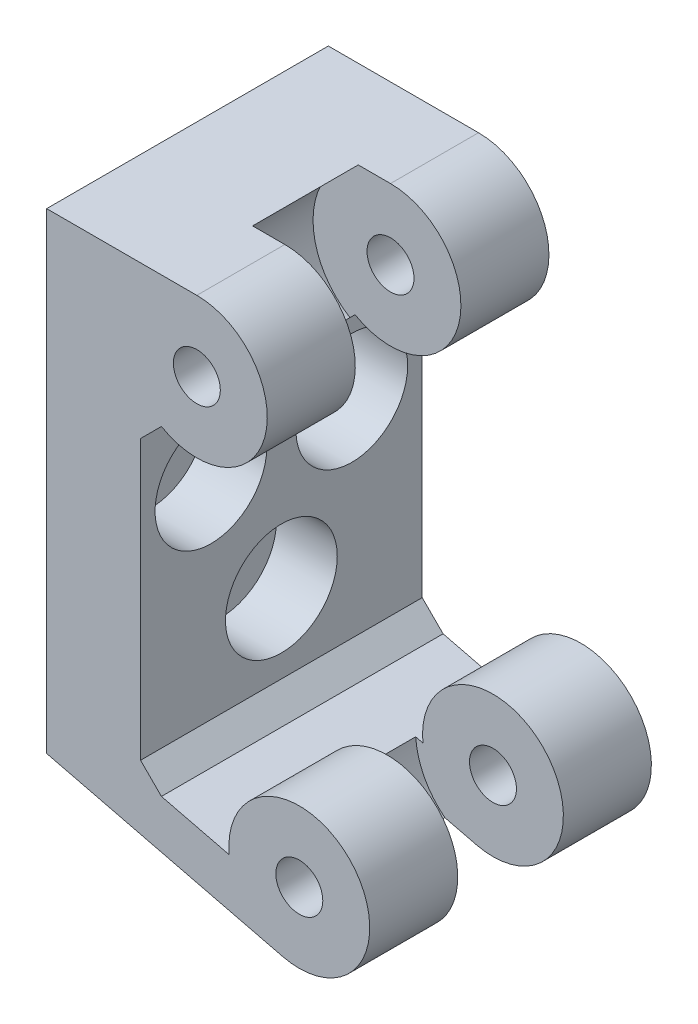
SolidWorks part; units mm, degrees
other "Markup1"
sketch "Sketch3" plane through (0, 0, 12) normal (0, 0, 1) x (1, 0, 0)
other "DetailItem1"
other "DetailItem3"
other "DetailItem5"
ref_plane "Front Plane" through (0, 0, 0) normal (0, 0, 1) x (1, 0, 0)
ref_plane "Top Plane" through (0, 0, 0) normal (0, 1, 0) x (1, 0, 0)
ref_plane "Right Plane" through (0, 0, 0) normal (1, 0, 0) x (0, 0, -1)
sketch "Sketch-optimization parameters" plane through (0, 0, 0) normal (0, 0, 1) x (1, 0, 0)
  line L2 (0, 0) -> (0, 20.1035)
  line L3 (0, 20.1035) -> (6.3989, 20.1035)
  line L5 (4.8896, 14.5108) -> (4, 13.6212)
  line L6 (4, 13.6212) -> (4, 1.7504)
  line L7 (4.8896, 0.8608) -> (7.7788, 0.1528)
  line L11 (6.3989, 17.1035) -> (10.764, 0.4507) construction
  line L16 (3.444, 0.5146) -> (10.764, 0.4507) construction
  line L17 (6.3989, -983.3033) -> (6.3989, 49016.6967) construction
  line L22 (4, 1.7504) -> (4.8896, 0.8608)
  line L23 (0, 0) -> (10.0499, -2.463)
  line L28 (-1000, 0) -> (49000, 0) construction
  line L29 (0, -1000) -> (0, 49000) construction
  line L30 (6.3655, 16.9158) -> (-8761.9708, -49208.2432) construction
  line L31 (-993.9512, 17.1035) -> (49006.0488, 17.1035) construction
  arc A0 (10.0499, -2.463) -> (7.7788, 0.1528) centre (10.764, 0.4507) ccw
  arc A1 (6.3989, 20.1035) -> (4.8896, 14.5108) centre (6.3989, 17.1035) cw
  circle A2 centre (6.3989, 17.1035) radius 1
  circle A3 centre (10.764, 0.4507) radius 1
  point P6 (2, 14.5175)
  point P13 (7.9172, 0)
  point P16 (7.83, 0)
  point P18 (9.6166, -2.6091)
  point P19 (5.6464, 0.6754)
  point P22 (4, 13.6212)
  dimension "D1" = 2
  dimension "D3" = 3
  dimension "D2" = 4
  dimension "D4" = 16.85
  dimension "D5" = 79.9
  dimension "D6" = 99.6
  dimension "D7" = 7.32
  dimension "D8" = 2
  dimension "D9" = 135
  dimension "D10" = 135
extrude "Boss-Extrude1" add sketch "Sketch-optimization parameters" along normal blind 12
ref_plane "midplane" through (0, 0, 6) normal (0, 0, 1) x (1, 0, 0)
sketch "Sketch2" plane through (0, 0, 6) normal (0, 0, 1) x (1, 0, 0)
  circle A0 centre (6.3989, 17.1035) radius 3.3
  circle A1 centre (10.764, 0.4507) radius 3.3
  dimension "D1" = 6.6
extrude "Cut-Extrude1" cut sketch "Sketch2" against normal blind 2.25 and the other way blind 2.25
ref_plane "Plane - base" [suppressed] through (-6.9825, 2.8211, 0) normal (-0.9272, 0.3746, 0) x (0, 0, -1)
sketch "Sketch4" [suppressed] plane through (-6.9825, 2.8211, 0) normal (-0.9272, 0.3746, 0) x (0, 0, -1)
  line L1 (-12, -18.6396) -> (0, -18.6396)
  line L2 (-12, -18.6396) -> (-12, 0)
  line L3 (-12, 0) -> (0, 0)
  line L4 (0, -18.6396) -> (0, 0)
extrude "Boss-Extrude2" [suppressed] add sketch "Sketch4" against normal up to surface up to face at (0, 10.0518, 6)
sketch "Hole sketch" plane through (4, 36.4446, 0) normal (-1, 0, 0) x (0, 0, -1)
  line L0 (-12, 25.8234) -> (0, 25.8234) construction
  line L3 (-6, -1.7766) -> (-6, 49998.2234) construction
  line L4 (-6, 44.0148) -> (-6, 28.8745) construction
  line L5 (-12, 28.8234) -> (-12, 22.8234) construction
  line L6 (-12, 17.9286) -> (-12, 44.7815) construction
  line L7 (-12, 31.3551) -> (-6, 31.3551) construction
  line L8 (0, 16.3411) -> (0, 36.4446) construction
  line L9 (-12, 22.8234) -> (0, 22.8234) construction
  line L10 (-12, 22.8234) -> (0, 22.8234) construction
  circle A0 centre (-9, 25.8234) radius 1.2884
  circle A1 centre (-3, 25.8234) radius 1.2884
  circle A2 centre (-6, 31.3551) radius 1.2884
  point P4 (-6, 26.277)
  point P5 (-6, 31.3551)
  point P8 (-9, 25.8234)
  point P9 (-3, 25.8234)
  point P10 (-6, 31.3551)
  point P25 (-3.0189, 25.393)
  dimension "D2" = 2.5768
  dimension "D1" = 3
  dimension "D3" = 3
extrude "Screw shaft holes" cut sketch "Hole sketch" against normal through all both and the other way through all
sketch "Sketch5" plane through (4, 26.1971, 0) normal (-1, 0, 0) x (0, 0, -1)
  circle A0 centre (-6, 21.1076) radius 2.3813
  circle A1 centre (-9, 15.5759) radius 2.3813
  circle A2 centre (-3, 15.5759) radius 2.3813
  dimension "D1" = 4.7625
extrude "Screw counterbores" cut sketch "Sketch5" along normal blind 2.5918
equation "\"axle-diameter\"=2"
equation "\"D1@Sketch-optimization parameters\" = \"axle-diameter\""
equation "\"switch-thickness\"=12"
equation "\"D1@Boss-Extrude1\"=\"switch-thickness\""
equation "\"base-width\"=4.0"
equation "\"axle-bushing-radius\"=3"
equation "\"D3@Sketch-optimization parameters\" = \"axle-bushing-radius\""
equation "\"D1@Sketch2\"=\"axle-bushing-radius\"*2.2"
equation "\"D1@Cut-Extrude1\"=\"switch-thickness\"/6+\"clearance\""
equation "\"D2@Cut-Extrude1\"=\"switch-thickness\"/6+\"clearance\""
equation "\"clearance\"= 0.25"
equation "\"arm-width\"=3.0"
equation "\"min-diameter\"=70"
